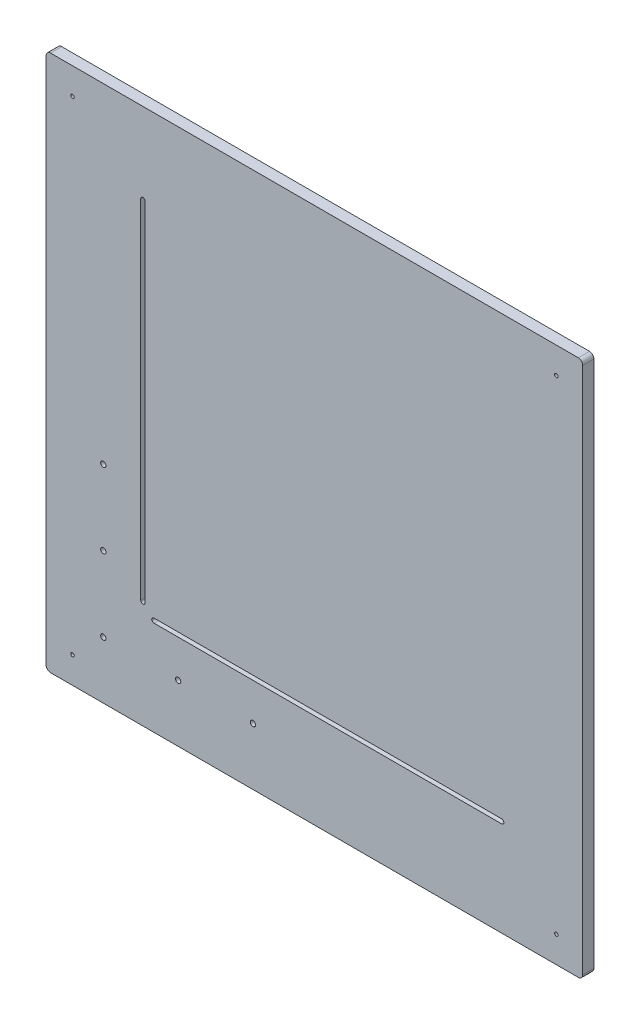
SolidWorks part; units mm, degrees
ref_plane "Front Plane" through (0, 0, 0) normal (0, 0, 1) x (1, 0, 0)
ref_plane "Top Plane" through (0, 0, 0) normal (0, 1, 0) x (1, 0, 0)
ref_plane "Right Plane" through (0, 0, 0) normal (1, 0, 0) x (0, 0, -1)
sketch "Sketch1" plane through (0, 0, 0) normal (0, 0, 1) x (1, 0, 0)
  line L1 (-152.4, -152.4) -> (152.4, -152.4)
  line L2 (-152.4, -152.4) -> (-152.4, 152.4)
  line L3 (-152.4, 152.4) -> (152.4, 152.4)
  line L4 (152.4, -152.4) -> (152.4, 152.4)
  line L5 (-152.4, -152.4) -> (152.4, 152.4) construction
  line L6 (-152.4, 152.4) -> (152.4, -152.4) construction
  point P0 (0, 0)
  dimension "D1" = 304.8
  dimension "D2" = 304.8
extrude "Boss-Extrude1" add sketch "Sketch1" along normal blind 6.35
hole_wizard "M3 Clearance Hole2" positions "Sketch2" profile "Sketch3" hole size "M3" standard "ANSI Metric" end condition up to next
sketch "Sketch2" plane through (0, 0, 6.35) normal (0, 0, 1) x (1, 0, 0)
  line L0 (152.4, -152.4) -> (152.4, 152.4) construction
  line L1 (152.4, 152.4) -> (-152.4, 152.4) construction
  line L2 (-152.4, -152.4) -> (152.4, -152.4) construction
  line L3 (-152.4, 152.4) -> (-152.4, -152.4) construction
  point P0 (137.4, 137.4)
  point P2 (-137.4, -137.4)
  point P4 (137.4, -137.4)
  point P6 (-137.4, 137.4)
  dimension "D1" = 15
  dimension "D2" = 15
  dimension "D3" = 15
  dimension "D4" = 15
sketch "Sketch3" plane through (137.4, 137.4, 6.35) normal (1, 0, 0) x (0, -1, 0)
  line L0 (0, 0) -> (0, 6.35)
  line L1 (0, 6.35) -> (1, 6.35)
  line L2 (1, 6.35) -> (1, 0)
  line L5 (1, 0) -> (0, 0)
  line L11 (0, -6.35) -> (0, 107.95) construction
  dimension "Thru Hole Dia." = 2
  dimension "Thru Hole Depth" = 6.35
fillet "Fillet1" radius 2.5 4 edges at (152.4, 152.4, 3.175) (152.4, -152.4, 3.175) (-152.4, -152.4, 3.175) (-152.4, 152.4, 3.175)
hole_wizard "M3 Clearance Slot1" positions "Sketch4" profile "Sketch5" size "M3" standard "ANSI Metric" slot yes end condition through all
sketch "Sketch4" plane through (0, 0, 6.35) normal (0, 0, 1) x (1, 0, 0)
  line L0 (-92.4, -97.4) -> (107.6, -97.4) construction
  line L1 (-149.9, -152.4) -> (149.9, -152.4) construction
  line L2 (-152.4, 149.9) -> (-152.4, -149.9) construction
  point P0 (7.6, -97.4)
  dimension "D1" = 55
  dimension "D2" = 200
  dimension "D3" = 60
sketch "Sketch5" plane through (7.6, -97.4, 6.35) normal (1, 0, 0) x (0, -1, 0)
  line L0 (0, 0) -> (0, 6.35)
  line L1 (0, 6.35) -> (1.25, 6.35)
  line L2 (1.25, 6.35) -> (1.25, 0)
  line L5 (1.25, 0) -> (0, 0)
  line L11 (0, -6.35) -> (0, 107.95) construction
  dimension "Thru Hole Dia." = 2.5
  dimension "Thru Hole Depth" = 6.35
hole_wizard "M3 Clearance Slot2" positions "Sketch6" profile "Sketch7" size "M3" standard "ANSI Metric" slot yes end condition through all
sketch "Sketch6" plane through (0, 0, 6.35) normal (0, 0, 1) x (1, 0, 0)
  line L0 (-97.4, 107.6) -> (-97.4, -92.4) construction
  line L1 (-152.4, 149.9) -> (-152.4, -149.9) construction
  line L2 (-149.9, -152.4) -> (149.9, -152.4) construction
  point P0 (-97.4, 7.6)
  dimension "D1" = 200
  dimension "D2" = 55
  dimension "D3" = 60
sketch "Sketch7" plane through (-97.4, 7.6, 6.35) normal (1, 0, 0) x (0, -1, 0)
  line L0 (0, 0) -> (0, 6.35)
  line L1 (0, 6.35) -> (1.25, 6.35)
  line L2 (1.25, 6.35) -> (1.25, 0)
  line L5 (1.25, 0) -> (0, 0)
  line L11 (0, -6.35) -> (0, 107.95) construction
  dimension "Thru Hole Dia." = 2.5
  dimension "Thru Hole Depth" = 6.35
hole_wizard "M3 Clearance Hole1" positions "Sketch8" profile "Sketch9" hole size "M3" standard "ANSI Metric" end condition through all
sketch "Sketch8" plane through (0, 0, 6.35) normal (0, 0, 1) x (1, 0, 0)
  point P0 (-34.9, -119.9)
  point P3 (-77.4, -119.9)
  point P6 (-119.9, -119.9)
  point P9 (-119.9, -77.4)
  point P12 (-119.9, -34.9)
sketch "Sketch9" plane through (-34.9, -119.9, 6.35) normal (1, 0, 0) x (0, -1, 0)
  line L0 (0, 0) -> (0, 6.35)
  line L1 (0, 6.35) -> (1.5, 6.35)
  line L2 (1.5, 6.35) -> (1.5, 0)
  line L5 (1.5, 0) -> (0, 0)
  line L11 (0, -6.35) -> (0, 107.95) construction
  dimension "Thru Hole Dia." = 3
  dimension "Thru Hole Depth" = 6.35
